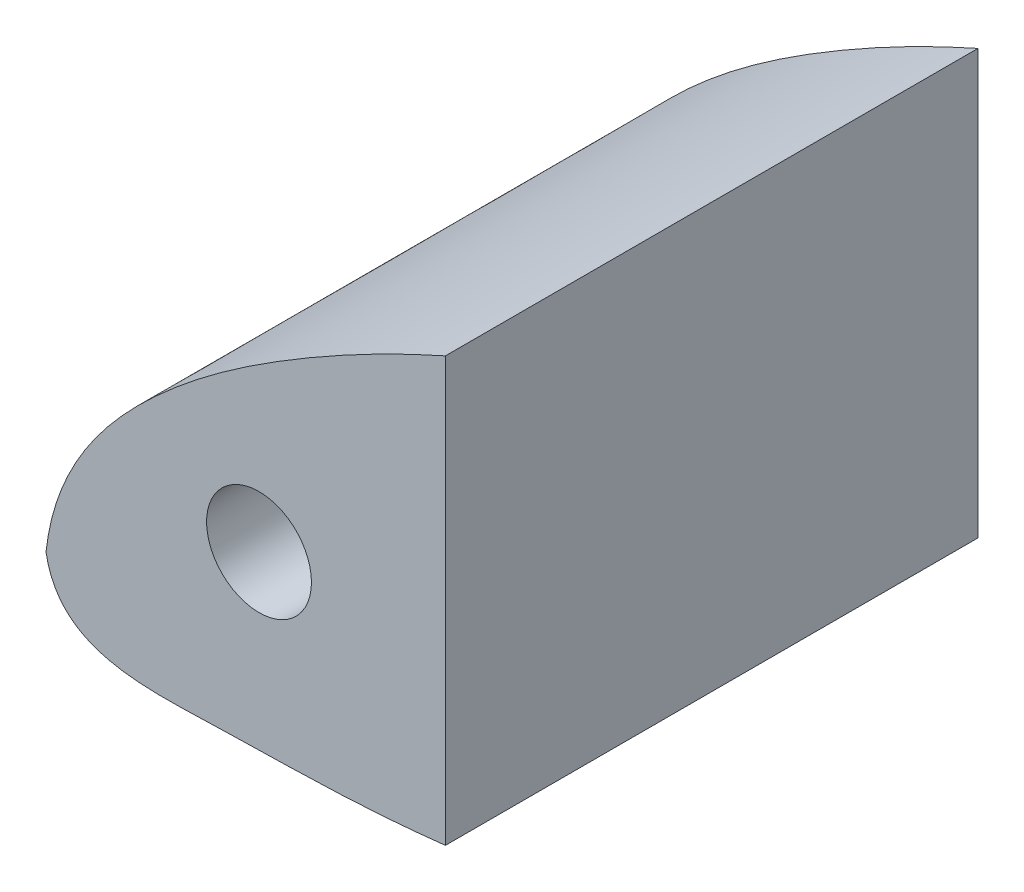
SolidWorks part; units mm, degrees
ref_plane "Front Plane" through (0, 0, 0) normal (0, 0, 1) x (1, 0, 0)
ref_plane "Top Plane" through (0, 0, 0) normal (0, 1, 0) x (1, 0, 0)
ref_plane "Right Plane" through (0, 0, 0) normal (1, 0, 0) x (0, 0, -1)
sketch "Sketch1" plane through (0, 0, 0) normal (0, 0, 1) x (1, 0, 0)
  spline S0 degree 3 poles (0.0006, 0.0001) (0.8106, 7.3592) (8.6491, 17.8566) (26.2867, 29.9752) (52.1111, 42.0692) (89.5976, 49.2908) (131.4008, 47.8848) (173.2567, 40.0411) (217.9611, 29.613) (256.9521, 19.5289) (290.3598, 8.711) (301.2732, 4.3828) (314.8169, -0.5162) (309.8463, 0.0001) knots 0 0 0 0 0.060864 0.113688 0.188609 0.312909 0.448482 0.557612 0.691544 0.852438 0.929756 0.976058 1 1 1 1
  spline S1 degree 3 poles (309.8463, 0.0001) (303.9568, 1.471) (293.9895, 2.094) (276.264, 4.5144) (260.8463, 5.4274) (235.8588, 7.8703) (205.1014, 8.8381) (157.7186, 9.0307) (110.4973, 6.1815) (66.5062, -0.5867) (36.4547, -6.0985) (15.3166, -6.1891) (1.2307, -6.9241) (0.0006, 0.0001) knots 0 0 0 0 0.057787 0.095275 0.171021 0.205339 0.335319 0.464904 0.658702 0.785512 0.893517 0.943092 1 1 1 1
extrude "Boss-Extrude1" add sketch "Sketch1" along normal blind 50.8
sketch "Sketch2" plane through (0, 0, 50.8) normal (0, 0, 1) x (1, 0, 0)
  circle A0 centre (20.32, 10.16) radius 5
  circle A1 centre (227.2963, 19.0501) radius 3.175
  dimension "D2" = 10
  dimension "D3" = 6.35
  dimension "D6" = 20.32
  dimension "D1" = 82.55
  dimension "D4" = 19.05
  dimension "D5" = 10.16
extrude "Cut-Extrude1" cut sketch "Sketch2" against normal through all
sketch "Sketch3" plane through (0, 0, 50.8) normal (0, 0, 1) x (1, 0, 0)
  line L1 (38.1, 71.718) -> (331.2889, 71.718)
  line L2 (38.1, 71.718) -> (38.1, -66.2532)
  line L3 (38.1, -66.2532) -> (331.2889, -66.2532)
  line L4 (331.2889, 71.718) -> (331.2889, -66.2532)
  dimension "D1" = 38.1
extrude "Cut-Extrude2" cut sketch "Sketch3" against normal through all
